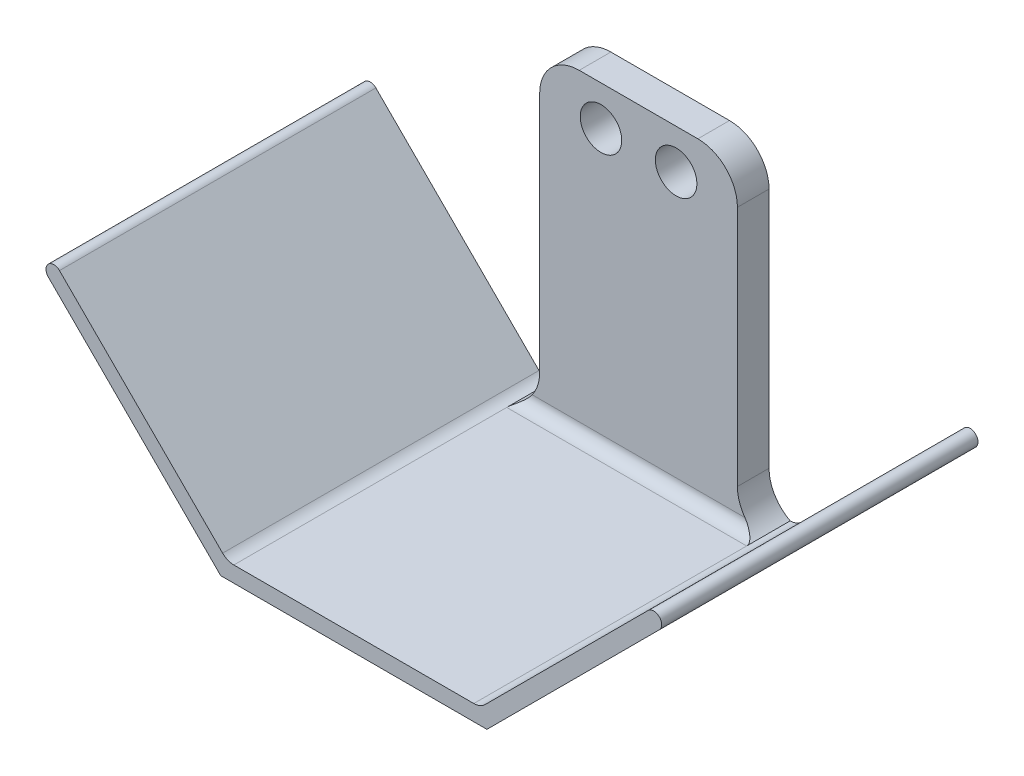
SolidWorks part; units mm, degrees
ref_plane "Front Plane" through (0, 0, 0) normal (0, 0, 1) x (1, 0, 0)
ref_plane "Top Plane" through (0, 0, 0) normal (0, 1, 0) x (1, 0, 0)
ref_plane "Right Plane" through (0, 0, 0) normal (1, 0, 0) x (0, 0, -1)
sketch "Sketch2" plane through (0, 0, 0) normal (0, 0, 1) x (1, 0, 0)
  line L0 (-32, 0) -> (32, 0)
  line L1 (32, 0) -> (74.4264, 42.4264)
  line L2 (-32, 0) -> (-74.4264, 42.4264)
  line L3 (-33.6569, -4) -> (-77.2548, 39.598)
  line L4 (-33.6569, -4) -> (33.6569, -4)
  line L5 (33.6569, -4) -> (77.2548, 39.598)
  arc A0 (-74.4264, 42.4264) -> (-77.2548, 39.598) centre (-75.8406, 41.0122) ccw
  arc A1 (74.4264, 42.4264) -> (77.2548, 39.598) centre (75.8406, 41.0122) cw
  point P4 (0, 0)
  dimension "D1" = 45
  dimension "D2" = 45
  dimension "D3" = 64
  dimension "D4" = 60
  dimension "D5" = 60
  dimension "D6" = 4
extrude "Boss-Extrude2" add sketch "Sketch2" along normal mid plane 80
fillet "Fillet1" radius 4 2 edges at (32, 0, 0) (-32, 0, 0)
sketch "Sketch3" plane through (0, 0, 0) normal (0, 1, 0) x (1, 0, 0)
  line L0 (30.3431, 40) -> (-30.3431, 40) construction
  line L1 (-25, 40) -> (25, 40)
  line L2 (-25, 40) -> (-25, 32)
  line L3 (-25, 32) -> (25, 32)
  line L4 (25, 40) -> (25, 32)
  point P6 (0, 32)
  dimension "D1" = 8
  dimension "D2" = 50
extrude "Boss-Extrude3" add sketch "Sketch3" along normal blind 80
sketch "Sketch4" plane through (0, 0, 0) normal (1, 0, 0) x (0, 0, -1)
  line L1 (40, 0) -> (32, 0) construction
  line L2 (-40, -4) -> (-40, 39.598) construction
  circle A0 centre (-10, 30) radius 30 construction
  dimension "D1" = 60
sketch "Sketch7" plane through (0, 0, -32) normal (0, 0, 1) x (1, 0, 0)
  line L0 (-25, 80) -> (25, 80) construction
  circle A0 centre (-10, 70) radius 7.5
  circle A1 centre (10, 70) radius 7.5
  dimension "D3" = 15
  dimension "D4" = 15
  dimension "D1" = 10
  dimension "D2" = 20
  dimension "D5" = 10
extrude "Boss-Extrude4" [suppressed] add sketch "Sketch7" along normal blind 10
sketch "Sketch5" plane through (0, 0, -32) normal (0, 0, 1) x (1, 0, 0)
  line L0 (-25, 80) -> (25, 80) construction
  circle A0 centre (-9.5, 70) radius 5.25
  circle A1 centre (9.5, 70) radius 5.25
  point P7 (12.2698, 47.4958)
  dimension "D1" = 10.5
  dimension "D2" = 10.5
  dimension "D4" = 10
  dimension "D5" = 9.5
  dimension "20" = 19
extrude "Cut-Extrude1" cut sketch "Sketch5" against normal through all
fillet "Fillet2" radius 10 4 edges at (25, 0, -36) (25, 80, -36) (-25, 80, -36) (-25, 0, -36)
fillet "Fillet3" radius 3 1 edges at (0, 0, -32)
equation "\"D5@Sketch5\" = \"20@Sketch5\" / 2"
equation "\"D5@Sketch7\"=\"D2@Sketch7\"/2"
